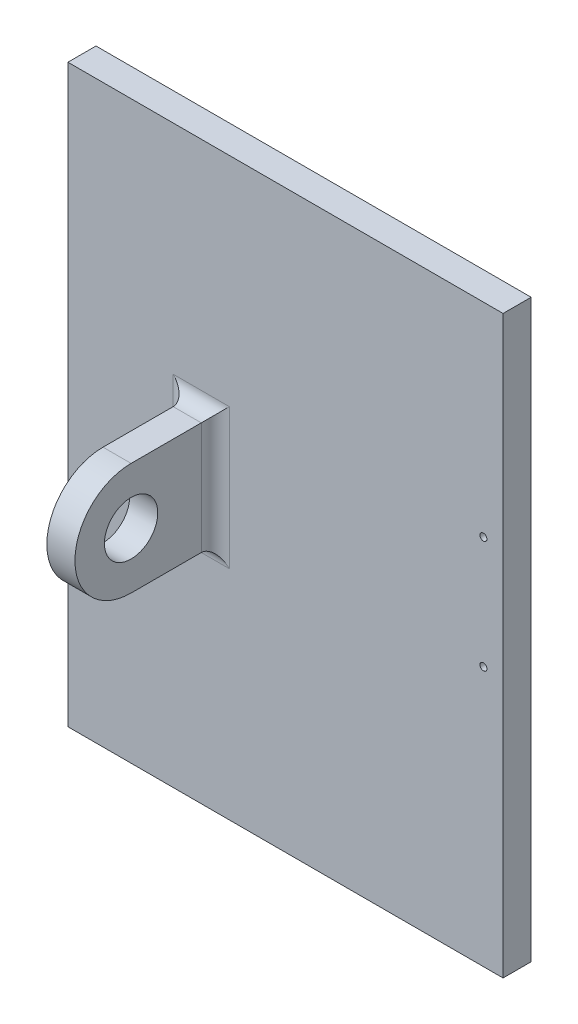
SolidWorks part; units mm, degrees
ref_plane "正面" through (0, 0, 0) normal (0, 0, 1) x (1, 0, 0)
ref_plane "平面" through (0, 0, 0) normal (0, 1, 0) x (1, 0, 0)
ref_plane "右側面" through (0, 0, 0) normal (1, 0, 0) x (0, 0, -1)
sketch "ｽｹｯﾁ2" plane through (0, 0, 0) normal (0, 0, 1) x (1, 0, 0)
  line L1 (-77.5, 102.5) -> (77.5, 102.5)
  line L2 (-77.5, 102.5) -> (-77.5, -102.5)
  line L3 (-77.5, -102.5) -> (77.5, -102.5)
  line L4 (77.5, 102.5) -> (77.5, -102.5)
  line L5 (-77.5, 102.5) -> (77.5, -102.5) construction
  line L6 (-77.5, -102.5) -> (77.5, 102.5) construction
  point P0 (0, 0)
  dimension "D1" = 155
  dimension "D2" = 205
extrude "ﾎﾞｽ - 押し出し1" add sketch "ｽｹｯﾁ2" along normal blind 10
sketch "ｽｹｯﾁ3" plane through (0, 0, 0) normal (0, 0, 1) x (1, 0, 0)
  line L0 (-35, 20) -> (-35, -20)
  line L1 (-35, -20) -> (-25, -20)
  line L2 (-25, -20) -> (-25, 20)
  line L3 (-25, 20) -> (-35, 20)
  dimension "D1" = 10
  dimension "D2" = 20
  dimension "D3" = 20
  dimension "D4" = 25
extrude "ﾎﾞｽ - 押し出し2" add sketch "ｽｹｯﾁ3" along normal blind 40
ref_plane "平面1" through (-35, 0, 0) normal (-1, 0, 0) x (0, 0, 1)
sketch "ｽｹｯﾁ4" plane through (-35, 0, 0) normal (-1, 0, 0) x (0, 0, 1)
  line L0 (40, 20) -> (40, -20) construction
  circle A0 centre (40, 0) radius 20
extrude "ﾎﾞｽ - 押し出し3" add sketch "ｽｹｯﾁ4" against normal blind 10
sketch "ｽｹｯﾁ5" plane through (-35, 0, 0) normal (-1, 0, 0) x (0, 0, 1)
  circle A0 centre (40, 0) radius 9.5
  dimension "D1" = 19
extrude "ｶｯﾄ - 押し出し1" cut sketch "ｽｹｯﾁ5" against normal blind 10
hole_wizard "M3x0.5 ねじ穴2" positions "ｽｹｯﾁ10" profile "ｽｹｯﾁ11" tap size "M3x0.5" standard "JIS" end condition through all
sketch "ｽｹｯﾁ10" plane through (0, 0, 10) normal (0, 0, 1) x (1, 0, 0)
  point P0 (70.5, -10.0009)
  point P3 (70.5, 29.9991)
sketch "ｽｹｯﾁ11" plane through (70.5, -10.0009, 10) normal (1, 0, 0) x (0, -1, 0)
  line L0 (0, 0) -> (0, 10)
  line L1 (0, 10) -> (1.25, 10)
  line L2 (1.25, 10) -> (1.25, 0)
  line L5 (1.25, 0) -> (0, 0)
  line L11 (0, -6.35) -> (0, 107.95) construction
  dimension "次ｻｰﾌｪｽまでのねじ下穴ﾄﾞﾘﾙ直径" = 2.5
  dimension "次ｻｰﾌｪｽまでのねじ下穴ﾄﾞﾘﾙの深さ" = 10
cosmetic thread "穴のねじ山4" parameters "D2"=3
cosmetic thread "穴のねじ山5" parameters "D2"=3
fillet "ﾌｨﾚｯﾄ1" radius 5 4 edges at (-30, -20, 10) (-35, 0, 10) (-30, 20, 10) (-25, 0, 10)
